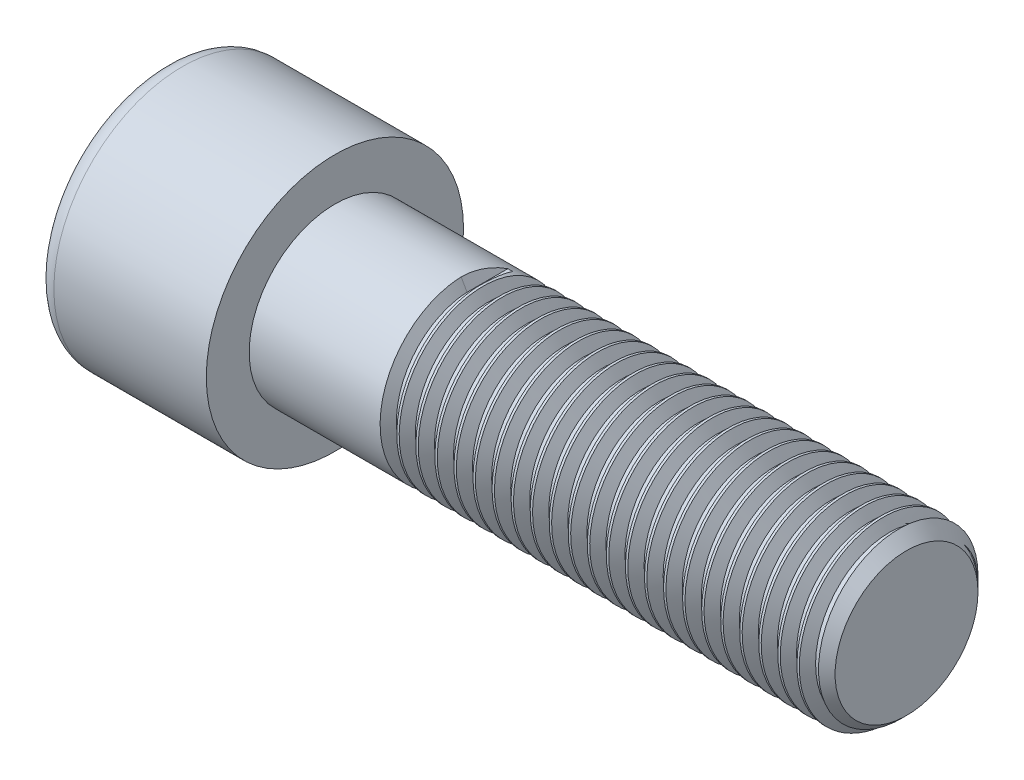
SolidWorks part; units mm, degrees
material "Latão"
ref_plane "Plano frontal" through (0, 0, 0) normal (0, 0, 1) x (1, 0, 0)
ref_plane "Plano superior" through (0, 0, 0) normal (0, 1, 0) x (1, 0, 0)
ref_plane "Plano direito" through (0, 0, 0) normal (1, 0, 0) x (0, 0, -1)
sketch "Esboço1" plane through (0, 0, 0) normal (0, 0, 1) x (1, 0, 0)
  line L0 (0, 0) -> (0, 27)
  line L1 (0, 27) -> (36, 27)
  line L2 (36, 27) -> (36, 18)
  line L3 (36, 18) -> (156, 18)
  line L4 (156, 18) -> (156, 0)
  line L5 (156, 0) -> (0, 0)
  dimension "D1" = 27
  dimension "D2" = 18
  dimension "D3" = 120
  dimension "D4" = 36
revolve "Revolução1" add sketch "Esboço1" angle 360 about L5
sketch "Esboço2" plane through (0, 0, 0) normal (-1, 0, 0) x (0, 0, 1)
  line L1 (0, 15.5885) -> (-13.5, 7.7942)
  line L2 (-13.5, 7.7942) -> (-13.5, -7.7942)
  line L3 (-13.5, -7.7942) -> (0, -15.5885)
  line L4 (0, -15.5885) -> (13.5, -7.7942)
  line L5 (13.5, -7.7942) -> (13.5, 7.7942)
  line L6 (13.5, 7.7942) -> (0, 15.5885)
  circle A0 centre (0, 0) radius 13.5 construction
  dimension "D1" = 27
extrude "Corte-extrusão1" cut sketch "Esboço2" against normal blind 20 contours L1 L2 L3 L4 L5 L6
sketch "Esboço3" plane through (20, 0, 0) normal (-1, 0, 0) x (0, 0, 1)
  point P0 (0, 0)
hole_wizard "Furo de diâmetro Ø27.0 (27)1" positions "Esboço3" profile "Esboço4" hole size "Ø27.0" standard "DIN"
sketch "Esboço4" plane through (20, 0, 0) normal (0, 1, 0) x (0, 0, 1)
  line L0 (0, 0) -> (0, 13.1116)
  line L1 (0, 13.1116) -> (13.5, 5)
  line L2 (13.5, 5) -> (13.5, 0)
  line L5 (13.5, 0) -> (0, 0)
  line L10 (0, 13.1116) -> (-13.5, 5) construction
  line L11 (0, -6.35) -> (0, 107.95) construction
  dimension "Hole Dia." = 27
  dimension "Hole Depth" = 5
  dimension "Drill Angle" = 118
fillet "Filete1" radius 4 1 edges at (0, 0, -27)
chamfer "Chanfro1" distance 3 angle 45 1 edges at (156, 0, -18)
thread "Rosca1" pitch 4 method cut profile "Perfil da rosca1" start angle 0, offset 10, length 97, pitch 4, diameter 36
ref_plane "Plano1" through (163, 0, 18) normal (0, -1, 0) x (0, 0, 1)
sketch "Perfil da rosca1" plane through (163, 0, 18) normal (0, -1, 0) x (0, 0, 1)
  line L0 (0, 0) -> (0, 4) construction
  line L11 (0, 0) -> (0, 3.5)
  line L12 (0, 3.5) -> (-2.1651, 2.25)
  line L13 (-2.1651, 2.25) -> (-2.1651, 1.25)
  line L15 (-2.1651, 1.25) -> (0, 0)
  line L17 (-2.1651, 1.75) -> (0, 1.75) construction
  point P2 (0, 0)
  dimension "Pitch" = 4
  dimension "Profile_Angle" = 60
  dimension "Profile_Land" = 1
  dimension "Profile_Height" = 2.1651
sketch "Esboço7" plane through (0, 0, 0) normal (0, 0, 1) x (1, 0, 0)
  line L4 (64.75, 15.8349) -> (66, 18)
  line L5 (66, 18) -> (62.5, 18)
  line L6 (62.5, 18) -> (63.75, 15.8349)
  line L7 (63.75, 15.8349) -> (64.75, 15.8349)
  line L8 (64.75, 15.8349) -> (66, 18)
  line L9 (66, 18) -> (62.5, 18)
  line L10 (62.5, 18) -> (63.75, 15.8349)
  line L11 (63.75, 15.8349) -> (64.75, 15.8349)
  point P2 (0, 0)
  dimension "D1" = 0
extrude "Corte-extrusão2" cut sketch "Esboço7" against normal blind 10
